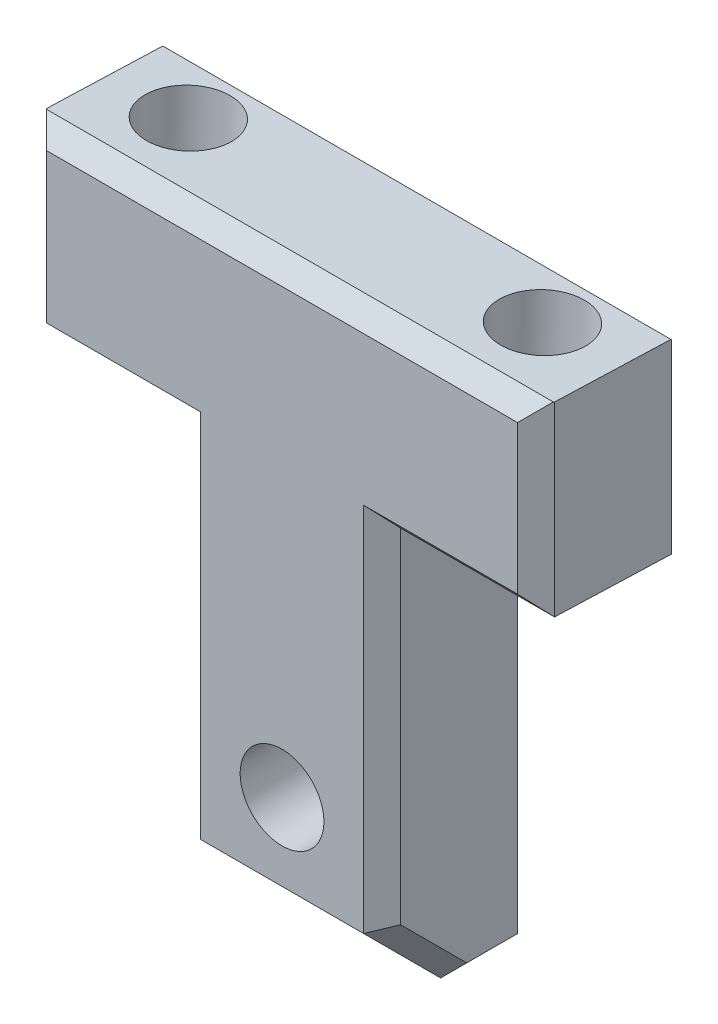
SolidWorks part; units mm, degrees
note: The reader was unsure of these and kept them because the rebuilt part matched: shared geometry of "Sketch2<4>", "Sketch6<2>".
material "PET"
ref_plane "Front Plane" through (0, 0, 0) normal (0, 0, 1) x (1, 0, 0)
ref_plane "Top Plane" through (0, 0, 0) normal (0, 1, 0) x (1, 0, 0)
ref_plane "Right Plane" through (0, 0, 0) normal (1, 0, 0) x (0, 0, -1)
sketch "Sketch1" plane through (0, 0, 0) normal (0, 0, 1) x (1, 0, 0)
  line L1 (-61.6436, -22.225) -> (-53.3886, -22.225)
  line L2 (-61.6436, -22.225) -> (-61.6436, 0)
  line L3 (-61.6436, 0) -> (-53.3886, 0)
  line L4 (-53.3886, -22.225) -> (-53.3886, 0)
  dimension "D1" = 22.225
  dimension "D2" = 8.255
extrude "Boss-Extrude1" add sketch "Sketch1" along normal blind 6.35
sketch "Sketch2" plane through (-61.6436, 0, 0) normal (-1, 0, 0) x (0, 0, 1)
  line L0 (0, 0) -> (0, -22.225) construction
  line L1 (6.35, 0) -> (0, 0)
  line L2 (6.35, 0) -> (6.35, -4.7625)
  line L3 (6.35, -4.7625) -> (0, -4.7625)
  line L4 (0, 0) -> (0, -4.7625)
  dimension "D1" = 4.7625
extrude "Boss-Extrude2" add sketch "Sketch2" along normal blind 6.35
extrude "Boss-Extrude3" add sketch "Sketch2<4>" against normal blind 6.35 from surface at -8.255 contours L1 L4 L3 L2 starting at face at (-53.3886, -11.1125, 3.175)
sketch "Sketch2<4>" plane through (-61.6436, 0, 0) normal (-1, 0, 0) x (0, 0, 1) same geometry as "Sketch2"
sketch "Sketch4" plane through (0, 0, 0) normal (0, 1, 0) x (1, 0, 0)
  line L4 (-47.0386, 0) -> (-67.9936, 0)
  line L5 (-67.9936, 0) -> (-67.9936, -6.35)
  line L6 (-67.9936, -6.35) -> (-47.0386, -6.35)
  line L7 (-47.0386, -6.35) -> (-47.0386, 0)
  line L8 (-47.0386, 0) -> (-67.9936, 0)
  line L9 (-67.9936, 0) -> (-67.9936, -6.35)
  line L10 (-67.9936, -6.35) -> (-47.0386, -6.35)
  line L11 (-47.0386, -6.35) -> (-47.0386, 0)
  dimension "D1" = 0
extrude "Boss-Extrude4" add sketch "Sketch4" along normal blind 3.1352
sketch "Sketch5" plane through (-67.9936, 0, 0) normal (-1, 0, 0) x (0, 0, 1)
  line L0 (0, 2.9168) -> (6.35, 3.1352)
  line L1 (0, 3.1352) -> (0, -4.7625) construction
  line L2 (6.35, 3.1352) -> (0, 3.1352)
  line L3 (0, 3.1352) -> (0, 2.9168)
  dimension "D1" = 1.97
extrude "Cut-Extrude3" cut sketch "Sketch5" against normal through all
sketch "Sketch6" plane through (-67.9936, 0, 0) normal (-1, 0, 0) x (0, 0, 1)
  line L0 (0, -4.7625) -> (6.35, -4.5441)
  line L1 (6.35, -4.7625) -> (6.35, 3.1352) construction
  line L2 (6.35, -4.5441) -> (6.35, -4.7625)
  line L3 (6.35, -4.7625) -> (0, -4.7625)
  dimension "D1" = 1.97
extrude "Cut-Extrude4" cut sketch "Sketch6" against normal up to surface (6.35 mm away) up to face at (-61.6436, -13.4937, 3.175)
extrude "Cut-Extrude5" cut sketch "Sketch6<2>" along normal up to surface (6.35 mm away) from surface at -20.955 up to face at (-53.3886, -13.4937, 3.175) starting at face at (-47.0386, -0.8682, 3.175)
sketch "Sketch6<2>" plane through (-67.9936, 0, 0) normal (-1, 0, 0) x (0, 0, 1) same geometry as "Sketch6"
hole_wizard "#4 Clearance Hole1" positions "Sketch11" profile "Sketch12" hole size "#4" standard "ANSI Inch" end condition through all
sketch "Sketch11" plane through (0, -4.7569, 0.1636) normal (0, -0.9994, 0.0344) x (-1, 0, 0)
  line L0 (53.3886, -6.19) -> (47.0386, 0.1637) construction
  line L2 (61.6436, -6.19) -> (67.9936, 0.1637) construction
  point P12 (64.8186, -3.0132)
  point P14 (50.2136, -3.0132)
sketch "Sketch12" plane through (-50.2136, -4.6533, 3.175) normal (1, 0, 0) x (0, -0.0344, -0.9994)
  line L0 (0, 0) -> (0, 7.8931)
  line L1 (0, 7.8931) -> (1.7272, 7.8931)
  line L2 (1.7272, 7.8931) -> (1.7272, 0)
  line L5 (1.7272, 0) -> (0, 0)
  line L11 (0, -6.35) -> (0, 107.95) construction
  dimension "Thru Hole Dia." = 3.4544
  dimension "Thru Hole Depth" = 7.8931
hole_wizard "#4 Clearance Hole2" positions "Sketch13" profile "Sketch14" hole size "#4" standard "ANSI Inch" end condition through all
sketch "Sketch13" plane through (0, 0, 0) normal (0, 0, -1) x (-1, 0, 0)
  point P0 (57.5161, -15.875)
sketch "Sketch14" plane through (-57.5161, -15.875, 0) normal (1, 0, 0) x (0, 1, 0)
  line L0 (0, 0) -> (0, 6.35)
  line L1 (0, 6.35) -> (1.7272, 6.35)
  line L2 (1.7272, 6.35) -> (1.7272, 0)
  line L5 (1.7272, 0) -> (0, 0)
  line L11 (0, -6.35) -> (0, 107.95) construction
  dimension "Thru Hole Dia." = 3.4544
  dimension "Thru Hole Depth" = 6.35
hole_wizard "Hole1" positions "Sketch15" profile "Sketch16" legacy
sketch "Sketch15" plane through (0, 0, 0) normal (0, 0, -1) x (-1, 0, 0)
  point P0 (57.5161, -15.875)
sketch "Sketch16" plane through (-57.5161, -15.875, 0) normal (1, 0, 0) x (0, 1, 0)
  line L0 (0, 0) -> (0, 3.429)
  line L1 (0, 3.429) -> (1.9431, 3.429)
  line L2 (1.9431, 3.429) -> (2.0701, 0)
  line L3 (2.0701, 0) -> (0, 0)
  line L4 (0, 110) -> (0, -10) construction
  dimension "Minor Diameter" = 3.8862
  dimension "Depth" = 3.429
  dimension "Major Diameter" = 4.1402
chamfer "Chamfer1" distance 3.175 angle 45 1 edges at (-57.5161, -22.225, 6.35)
chamfer "Chamfer2" distance 0.762 angle 45 19 edges at (-50.2136, -4.7625, 0) (-50.2136, -4.5441, 6.35) (-47.0386, -0.9228, 0) (-57.5161, 3.1352, 6.35) (-57.5161, 2.9168, 0) (-67.9936, -0.9228, 0) (-64.8186, -4.5441, 6.35) (-64.8186, -4.7625, 0) (-53.3886, -20.6375, 4.7625) (-61.6436, -20.6375, 4.7625) (-53.3886, -22.225, 1.5875) (-61.6436, -22.225, 1.5875) (-53.3886, -13.4938, 0) (-57.5161, -22.225, 0) (-61.6436, -13.4937, 0) (-67.9936, -0.7044, 6.35) (-47.0386, -0.7044, 6.35) (-61.6436, -11.797, 6.35) (-53.3886, -11.797, 6.35)
